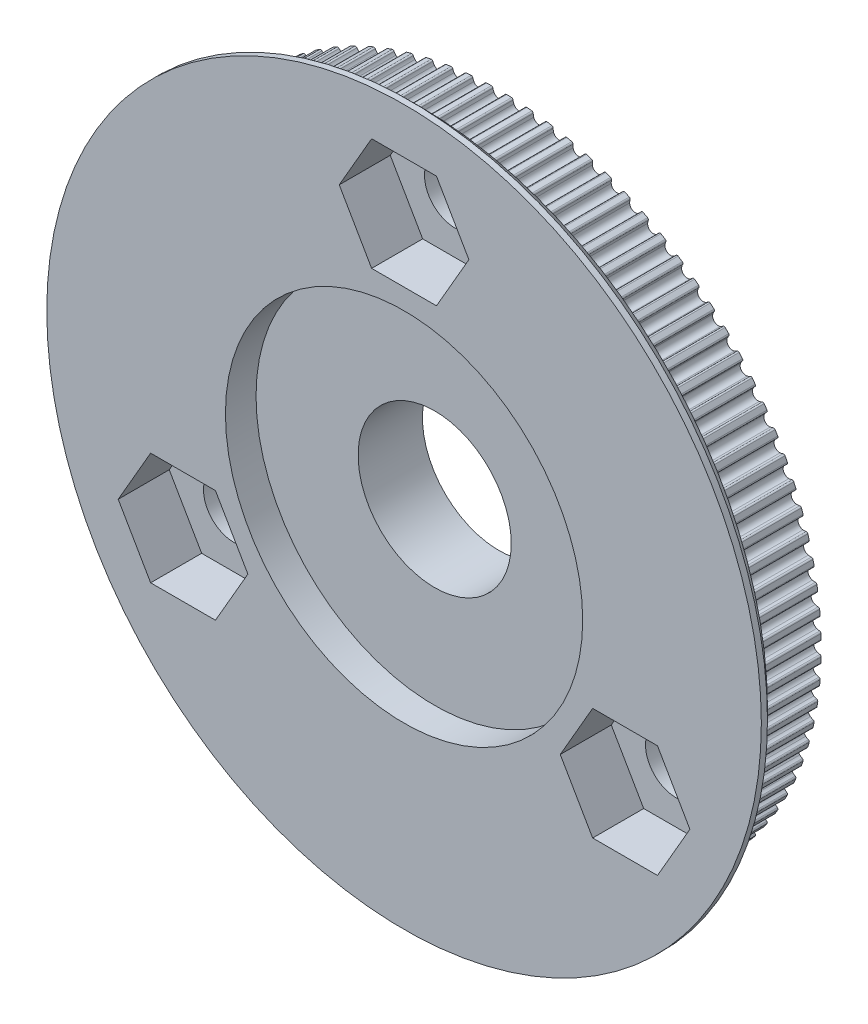
SolidWorks part; units mm, degrees
ref_plane "Front Plane" through (0, 0, 0) normal (0, 0, 1) x (1, 0, 0)
ref_plane "Top Plane" through (0, 0, 0) normal (0, 1, 0) x (1, 0, 0)
ref_plane "Right Plane" through (0, 0, 0) normal (1, 0, 0) x (0, 0, -1)
sketch "Sketch1" plane through (0, 0, 0) normal (0, 0, 1) x (1, 0, 0)
  circle A112 centre (0, 0) radius 31.83
  dimension "D2" = 63.66
extrude "Boss-Extrude3" add sketch "Sketch1" along normal blind 7.7
sketch "Sketch35" plane through (0, 0, 7.7) normal (0, 0, 1) x (1, 0, 0)
  line L0 (0, 0) -> (0, 31.575) construction
  line L1 (0, 0) -> (1.0056, 31.559) construction
  line L2 (0, 0) -> (-1.0056, 31.559) construction
  line L3 (-1.0056, 31.559) -> (-1.0137, 31.8139)
  line L4 (1.0056, 31.559) -> (1.0137, 31.8139)
  circle A1 centre (0, 0) radius 31.83
  arc A2 (1.0137, 31.8139) -> (-1.0137, 31.8139) centre (0, 0) ccw
  arc A5 (-0.5927, 31.4366) -> (-0.7448, 31.5662) centre (-0.7413, 31.4163) ccw
  arc A6 (-0.5927, 31.4366) -> (-0.5066, 31.1464) centre (0.3981, 31.5725) ccw
  arc A7 (-0.5066, 31.1464) -> (0.5066, 31.1464) centre (0, 31.385) ccw
  arc A8 (-0.7448, 31.5662) -> (-1.0056, 31.559) centre (0, 0) ccw
  arc A9 (0.5927, 31.4366) -> (0.5066, 31.1464) centre (-0.3981, 31.5725) cw
  arc A10 (0.5927, 31.4366) -> (0.7448, 31.5662) centre (0.7413, 31.4163) cw
  arc A11 (0.7448, 31.5662) -> (1.0056, 31.559) centre (0, 0) cw
  circle A12 centre (0, 0) radius 31.83 construction
  dimension "D5" = 0.56
  dimension "D7" = 0.19
  dimension "D9" = 0.56
  dimension "D10" = 1
  dimension "D11" = 0.15
  dimension "D3" = 1.825
  dimension "D4" = 1.825
  dimension "D12" = 3.65
  dimension "D13" = 0.3981
  dimension "D1" = 0
extrude "Cut-Extrude18" cut sketch "Sketch35" against normal blind 7.7
pattern_circular "CirPattern1" count 100 every 3.6 about axis through (0, 0, 7.7) along (0, 0, 1) of "Cut-Extrude18"
sketch "Sketch36" plane through (0, 0, 7.7) normal (0, 0, 1) x (1, 0, 0)
  circle A0 centre (0, 0) radius 7.5
  dimension "D1" = 15
extrude "Cut-Extrude19" cut sketch "Sketch36" against normal blind 7.7
sketch "Sketch37" plane through (0, 0, 7.7) normal (0, 0, 1) x (1, 0, 0)
  circle A0 centre (0, 0) radius 35
  dimension "D1" = 70
extrude "Boss-Extrude4" add sketch "Sketch37" along normal blind 1.6
sketch "Sketch38" plane through (0, 0, 9.3) normal (0, 0, 1) x (1, 0, 0)
  circle A4 centre (0, 25) radius 3
  circle A5 centre (21.6506, -12.5) radius 3
  circle A6 centre (-21.6506, -12.5) radius 3
  point P10 (0, 0)
  dimension "D1" = 25
  dimension "D2" = 6
  dimension "D3" = 3
extrude "Cut-Extrude20" cut sketch "Sketch38" against normal through all
chamfer "Chamfer1" distance 1 angle 45 1 edges at (35, 0, 7.7)
sketch "Sketch40" plane through (0, 0, 7.7) normal (0, 0, -1) x (-1, 0, 0)
  circle A0 centre (0, 0) radius 7.5
extrude "Cut-Extrude22" cut sketch "Sketch40" against normal through all
sketch "Sketch41" plane through (0, 0, 9.3) normal (0, 0, 1) x (1, 0, 0)
  circle A0 centre (0, 0) radius 17.5
  dimension "D1" = 35
extrude "Cut-Extrude23" cut sketch "Sketch41" against normal blind 3
sketch "Sketch42" plane through (0, 0, 9.3) normal (0, 0, 1) x (1, 0, 0)
  line L1 (6.3509, 25) -> (3.1754, 30.5)
  line L2 (3.1754, 30.5) -> (-3.1754, 30.5)
  line L3 (-3.1754, 30.5) -> (-6.3509, 25)
  line L4 (-6.3509, 25) -> (-3.1754, 19.5)
  line L5 (-3.1754, 19.5) -> (3.1754, 19.5)
  line L6 (3.1754, 19.5) -> (6.3509, 25)
  line L24 (18.4752, -18) -> (24.8261, -18)
  line L25 (24.8261, -18) -> (28.0015, -12.5)
  line L26 (28.0015, -12.5) -> (24.8261, -7)
  line L27 (24.8261, -7) -> (18.4752, -7)
  line L28 (18.4752, -7) -> (15.2998, -12.5)
  line L29 (15.2998, -12.5) -> (18.4752, -18)
  line L30 (-24.8261, -7) -> (-28.0015, -12.5)
  line L31 (-28.0015, -12.5) -> (-24.8261, -18)
  line L32 (-24.8261, -18) -> (-18.4752, -18)
  line L33 (-18.4752, -18) -> (-15.2998, -12.5)
  line L34 (-15.2998, -12.5) -> (-18.4752, -7)
  line L35 (-18.4752, -7) -> (-24.8261, -7)
  circle A0 centre (0, 25) radius 5.5 construction
  circle A1 centre (21.6506, -12.5) radius 5.5 construction
  circle A2 centre (-21.6506, -12.5) radius 5.5 construction
  point P28 (0, 0)
  dimension "D1" = 11
extrude "Cut-Extrude26" cut sketch "Sketch42" against normal blind 5
